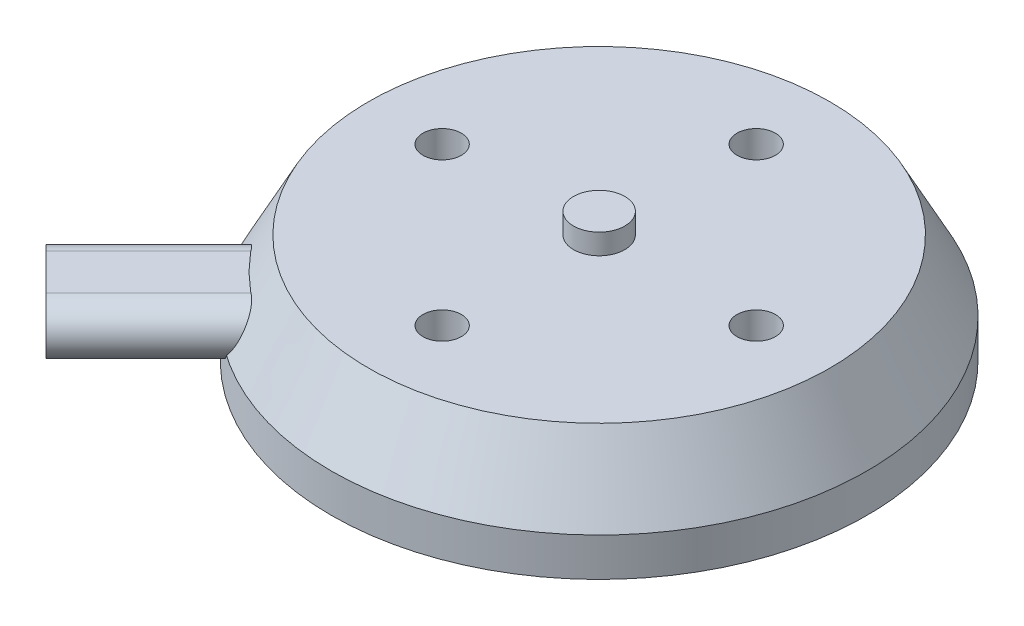
SolidWorks part; units mm, degrees
ref_plane "Plan de face" through (0, 0, 0) normal (0, 0, 1) x (1, 0, 0)
ref_plane "Plan de dessus" through (0, 0, 0) normal (0, 1, 0) x (1, 0, 0)
ref_plane "Plan de droite" through (0, 0, 0) normal (1, 0, 0) x (0, 0, -1)
sketch "Esquisse3" plane through (0, 0, 0) normal (0, 0, 1) x (1, 0, 0)
  line L0 (0, 0) -> (0, 30.2322) construction
  line L1 (-20.9, 0) -> (-20.9, 3)
  line L2 (-20.9, 0) -> (0, 0)
  line L3 (0, 8.5) -> (0, 0)
  line L4 (-20.9, 3) -> (-18, 8.5)
  line L5 (-18, 8.5) -> (0, 8.5)
  point P7 (-18, 8.5)
  dimension "D1" = 20.9
  dimension "D2" = 3
  dimension "D3" = 8.5
  dimension "D4" = 18
revolve "Révolution1" add sketch "Esquisse3" angle 360 about L0
sketch "Esquisse4" plane through (0, 8.5, 0) normal (0, 1, 0) x (1, 0, 0)
  line L0 (-12.25, 0) -> (12.25, 0) construction
  line L1 (3.7689, -3.7689) -> (0, 0) construction
  line L2 (0, 12.25) -> (0, -12.25) construction
  circle A0 centre (12.25, 0) radius 1.5
  circle A1 centre (-12.25, 0) radius 1.5
  circle A2 centre (0, -12.25) radius 1.5
  circle A3 centre (0, 12.25) radius 1.5
  dimension "D1" = 3
  dimension "D3" = 3
  dimension "D4" = 45
  dimension "D2" = 24.5
extrude "Enlèv. mat.-Extru.1" cut sketch "Esquisse4" against normal up to next
sketch "Esquisse5" plane through (0, 8.5, 0) normal (0, 1, 0) x (1, 0, 0)
  circle A0 centre (0, 0) radius 2
  dimension "D1" = 4
extrude "Boss.-Extru.2" add sketch "Esquisse5" along normal blind 1.6 separate body
sketch "Esquisse6" plane through (0, 0, 0) normal (0, -1, 0) x (1, 0, 0)
  line L0 (0, 0) -> (-14.7785, 14.7785) construction
  line L1 (-12.25, 0) -> (0, 12.25) construction
  line L2 (-17.3338, 11.6769) -> (-11.6769, 17.3338) construction
  line L3 (-17.3338, 11.6769) -> (-24.4048, 18.748)
  line L4 (-24.4048, 18.748) -> (-18.748, 24.4048)
  line L5 (-18.748, 24.4048) -> (-11.6769, 17.3338)
  line L6 (-24.4048, 18.748) -> (-18.748, 24.4048)
  line L7 (-24.4048, 18.748) -> (-2.8284, -2.8284)
  line L8 (-18.748, 24.4048) -> (2.8284, 2.8284)
  line L9 (-2.8284, -2.8284) -> (2.8284, 2.8284)
  circle A1 centre (0, 0) radius 20.9 construction
  point P11 (-14.5053, 14.5053)
  circle M9 centre (0, 0) radius 20.9
  dimension "D1" = 8
  dimension "D2" = 10
extrude "Boss.-Extru.4" add sketch "Esquisse6" against normal blind 4 from offset 2 separate body contours L5 L4 L3 M9 | L7 L9 L8 M9 region at (-7.3441, 0, 7.3441) region at (-18.1316, 0, 18.1316) offset against normal yes
fillet "Congé3" 2 edges at (-7.9598, 6, 13.6166) (-7.9598, 2, 13.6166) type full round first side face at (-10.7882, 6, 10.7882) second side face at (-10.7882, 2, 10.7882) middle face at (-7.9598, 4, 13.6166)
fillet "Congé2" 2 edges at (-13.6166, 6, 7.9598) (-13.6166, 2, 7.9598) type full round first side face at (-11.4953, 6, 10.0811) second side face at (-11.4953, 2, 10.0811) middle face at (-13.6166, 4, 7.9598)
